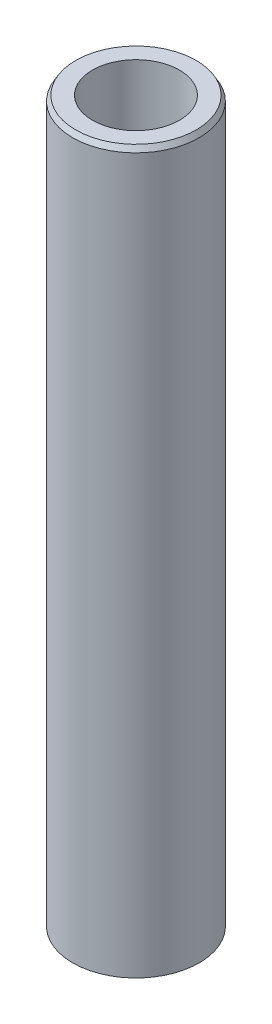
SolidWorks part; units mm, degrees
ref_plane "Front Plane" through (0, 0, 0) normal (0, 0, 1) x (1, 0, 0)
ref_plane "Top Plane" through (0, 0, 0) normal (0, 1, 0) x (1, 0, 0)
ref_plane "Right Plane" through (0, 0, 0) normal (1, 0, 0) x (0, 0, -1)
sketch "Sketch1" plane through (0, 0, 0) normal (0, 1, 0) x (1, 0, 0)
  circle A0 centre (0, 0) radius 52.5
  dimension "SHAFT_OD" = 105
extrude "Boss-Extrude1" add sketch "Sketch1" along normal blind 600
sketch "Sketch2" plane through (0, 0, 0) normal (0, 1, 0) x (1, 0, 0)
  circle A0 centre (0, 0) radius 36.1077
  dimension "BORE_D" = 72.2154
extrude "Cut-Extrude1" cut sketch "Sketch2" along normal through all
chamfer "Chamfer1" distance 4.3598 angle 30 2 edges at (0, 600, 52.5) (0, 0, 52.5) first distance on face at (0, 600, 52.5) first distance on face at (0, 0, 36.1077)
